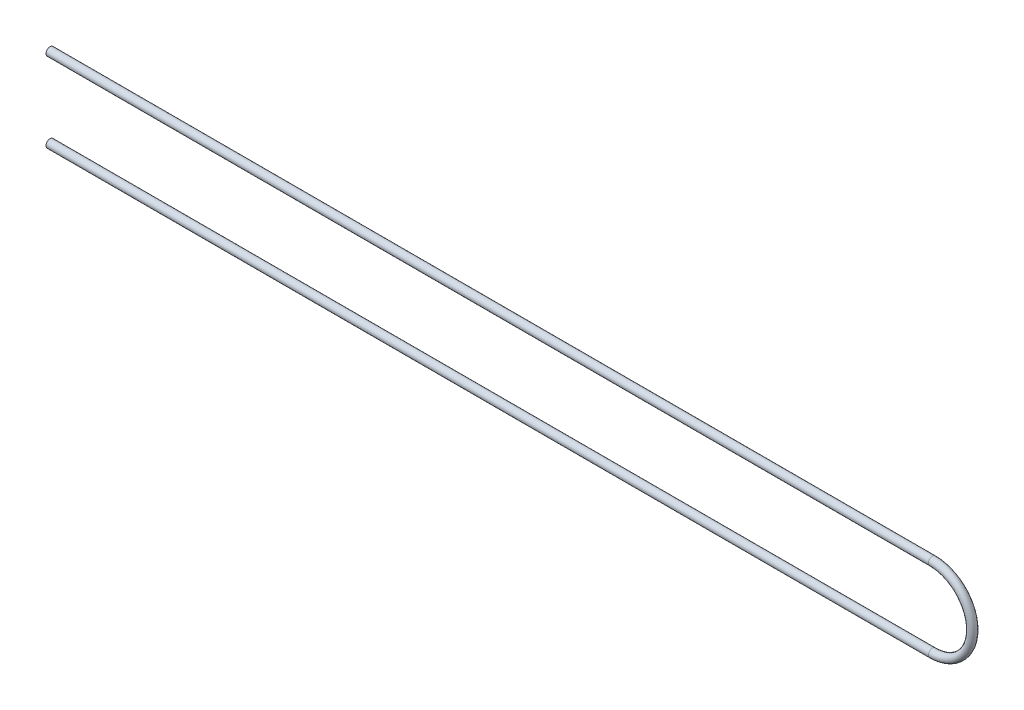
SolidWorks part; units mm, degrees
ref_plane "Front Plane" through (0, 0, 0) normal (0, 0, 1) x (1, 0, 0)
ref_plane "Top Plane" through (0, 0, 0) normal (0, 1, 0) x (1, 0, 0)
ref_plane "Right Plane" through (0, 0, 0) normal (1, 0, 0) x (0, 0, -1)
sketch "Sketch1" plane through (0, 0, 0) normal (0, 0, 1) x (1, 0, 0)
  line L0 (0, 0) -> (2325, 0)
  line L1 (2325, -210) -> (0, -210)
  arc A0 (2325, 0) -> (2325, -210) centre (2325, -105) cw
  dimension "D1" = 2325
  dimension "D2" = 105
sweep "Sweep-Thin1" add path "Sketch1" circular profile diameter 21.3 parameters "D1"=0.5, "D3"=21.3
